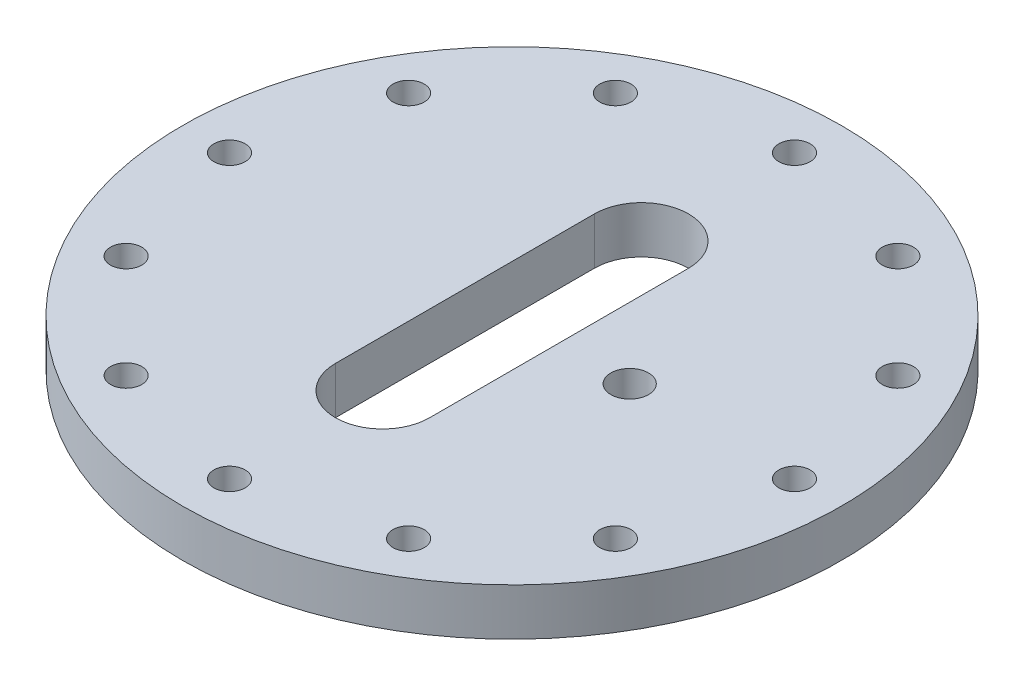
SolidWorks part; units mm, degrees
ref_plane "Front Plane" through (0, 0, 0) normal (0, 0, 1) x (1, 0, 0)
ref_plane "Top Plane" through (0, 0, 0) normal (0, 1, 0) x (1, 0, 0)
ref_plane "Right Plane" through (0, 0, 0) normal (1, 0, 0) x (0, 0, -1)
sketch "Sketch2" plane through (0, 0, 0) normal (0, 0, 1) x (1, 0, 0)
  line L0 (0, 0) -> (-88.9, 0)
  line L1 (-88.9, 0) -> (-88.9, 12.7)
  line L2 (-88.9, 12.7) -> (0, 12.7)
  line L3 (0, 12.7) -> (0, 0)
  dimension "D1" = 12.7
  dimension "D2" = 88.9
revolve "Revolve1" add sketch "Sketch2" angle 360 about L3
sketch "Sketch3" plane through (0, 12.7, 0) normal (0, 1, 0) x (1, 0, 0)
  line L0 (-12.7, 34.925) -> (-12.7, -34.925)
  line L1 (12.7, 34.925) -> (12.7, -34.925)
  line L2 (0, -34.925) -> (0, 34.925) construction
  arc A0 (-12.7, 34.925) -> (12.7, 34.925) centre (0, 34.925) cw
  arc A1 (-12.7, -34.925) -> (12.7, -34.925) centre (0, -34.925) ccw
  point P5 (0, 0)
  dimension "D2" = 12.7
  dimension "D1" = 69.85
extrude "Cut-Extrude1" cut sketch "Sketch3" against normal through all
hole_wizard "5/16 Clearance Hole1" positions "Sketch5" profile "Sketch4" hole size "5/16" standard "ANSI Inch" end condition through all
sketch "Sketch5" plane through (0, 12.7, 0) normal (0, 1, 0) x (1, 0, 0)
  line L0 (0, 0) -> (0, 76.2) construction
  point P0 (0, 76.2)
  dimension "D1" = 76.2
sketch "Sketch4" plane through (0, 12.7, -76.2) normal (1, 0, 0) x (0, 0, 1)
  line L0 (0, 0) -> (0, 12.7)
  line L1 (0, 12.7) -> (4.2164, 12.7)
  line L2 (4.2164, 12.7) -> (4.2164, 0)
  line L5 (4.2164, 0) -> (0, 0)
  line L11 (0, -6.35) -> (0, 107.95) construction
  dimension "Thru Hole Dia." = 8.4328
  dimension "Thru Hole Depth" = 12.7
ref_axis "Axis1" through (0, 13.335, 0) along (0, -1, 0)
pattern_circular "CirPattern1" count 12 over 360 about axis through (0, 13.335, 0) along (0, -1, 0) of "5/16 Clearance Hole1"
hole_wizard "5/16 Clearance Hole2" positions "Sketch6" profile "Sketch7" hole size "5/16" standard "ANSI Inch" end condition through all
sketch "Sketch6" plane through (0, 12.7, 0) normal (0, 1, 0) x (1, 0, 0)
  line L0 (0, 0) -> (31.75, 0) construction
  point P0 (31.75, 0)
  dimension "D1" = 31.75
sketch "Sketch7" plane through (31.75, 12.7, 0) normal (1, 0, 0) x (0, 0, 1)
  line L0 (0, 0) -> (0, 12.7)
  line L1 (0, 12.7) -> (5.08, 12.7)
  line L2 (5.08, 12.7) -> (5.08, 0)
  line L5 (5.08, 0) -> (0, 0)
  line L11 (0, -6.35) -> (0, 107.95) construction
  dimension "Thru Hole Dia." = 10.16
  dimension "Thru Hole Depth" = 12.7
